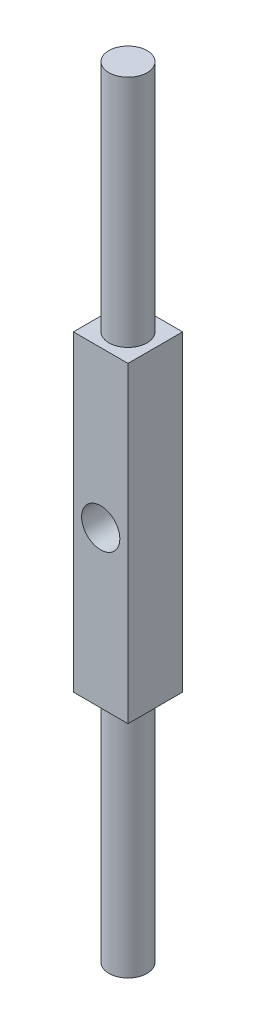
SolidWorks part; units mm, degrees
ref_plane "Front Plane" through (0, 0, 0) normal (0, 0, 1) x (1, 0, 0)
ref_plane "Top Plane" through (0, 0, 0) normal (0, 1, 0) x (1, 0, 0)
ref_plane "Right Plane" through (0, 0, 0) normal (1, 0, 0) x (0, 0, -1)
sketch "Sketch1" plane through (0, 0, 0) normal (0, 1, 0) x (1, 0, 0)
  circle A0 centre (0, 0) radius 2.45
  dimension "D1" = 4.9
extrude "Boss-Extrude1" add sketch "Sketch1" along normal blind 50
extrude "Boss-Extrude2" add sketch "Sketch1<2>" against normal blind 50
sketch "Sketch1<2>" plane through (0, 0, 0) normal (0, 1, 0) x (1, 0, 0) same geometry as "Sketch1"
sketch "Sketch2" plane through (0, 0, 0) normal (0, 1, 0) x (1, 0, 0)
  line L1 (-3.5, 3.5) -> (3.5, 3.5)
  line L2 (-3.5, 3.5) -> (-3.5, -3.5)
  line L3 (-3.5, -3.5) -> (3.5, -3.5)
  line L4 (3.5, 3.5) -> (3.5, -3.5)
  line L5 (-3.5, 3.5) -> (3.5, -3.5) construction
  line L6 (-3.5, -3.5) -> (3.5, 3.5) construction
  point P0 (0, 0)
  dimension "D1" = 7
  dimension "D2" = 7
extrude "Boss-Extrude3" add sketch "Sketch2" along normal blind 20
extrude "Boss-Extrude4" add sketch "Sketch2<2>" against normal blind 20
sketch "Sketch2<2>" plane through (0, 0, 0) normal (0, 1, 0) x (1, 0, 0) same geometry as "Sketch2"
sketch "Sketch3" plane through (0, 0, 3.5) normal (0, 0, 1) x (1, 0, 0)
  circle A0 centre (0, 0) radius 2.45
  dimension "D1" = 4.9
extrude "Cut-Extrude1" cut sketch "Sketch3" against normal through all
sketch "Sketch4" plane through (0, 0, 0) normal (0, 1, 0) x (1, 0, 0)
  line L0 (-2.45, -3.5) -> (-1.96, -3.325)
  line L1 (-1.96, -2.875) -> (-2.45, -2.7)
  line L2 (-2.45, -3.5) -> (-2.45, -2.7)
  line L7 (-1.96, -3.325) -> (-1.96, -2.875)
  point P4 (-2.45, -3.1)
  dimension "D1" = 0.8
  dimension "D3" = 0.45
sketch "Sketch7" plane through (0, 0, 3.5) normal (0, 0, 1) x (1, 0, 0)
  circle A0 centre (0, 0) radius 2.45
curve "Helix/Spiral1" pitch 4 height 7 turns 1.75
sketch "Sketch9" plane through (0, 0, 0) normal (0, 1, 0) x (1, 0, 0)
  line L0 (0, -3.7334) -> (0, 1.2476)
